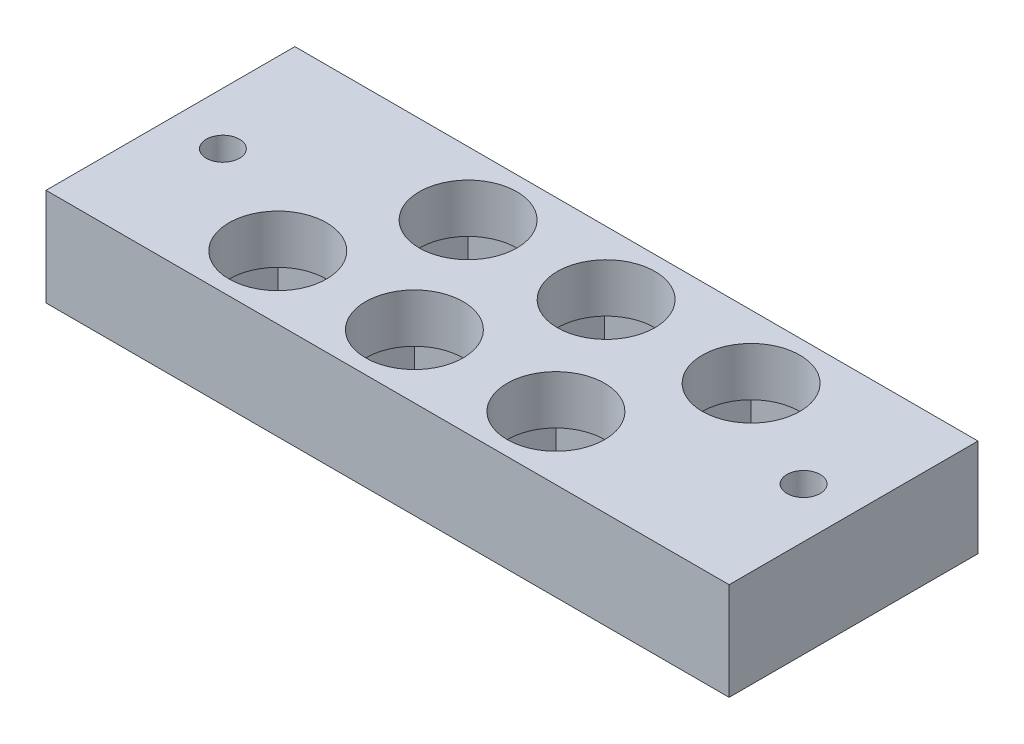
SolidWorks part; units mm, degrees
ref_plane "Front Plane" through (0, 0, 0) normal (0, 0, 1) x (1, 0, 0)
ref_plane "Top Plane" through (0, 0, 0) normal (0, 1, 0) x (1, 0, 0)
ref_plane "Right Plane" through (0, 0, 0) normal (1, 0, 0) x (0, 0, -1)
sketch "Sketch1" plane through (0, 0, 0) normal (0, 1, 0) x (1, 0, 0)
  line L0 (-35, 12.75) -> (-35, -12.75)
  line L1 (-35, -12.75) -> (35, -12.75)
  line L2 (35, -12.75) -> (35, 12.75)
  line L3 (35, 12.75) -> (-35, 12.75)
  line L4 (-23.75, -0.25) -> (-23.75, -12.25)
  line L5 (-23.75, -12.25) -> (-11.75, -12.25)
  line L6 (-11.75, -12.25) -> (-11.75, -0.25)
  line L7 (-11.75, -0.25) -> (-23.75, -0.25)
  line L8 (-9.75, -0.25) -> (-9.75, -12.25)
  line L9 (-9.75, -12.25) -> (2.25, -12.25)
  line L10 (2.25, -12.25) -> (2.25, -0.25)
  line L11 (2.25, -0.25) -> (-9.75, -0.25)
  line L12 (4.75, -0.25) -> (16.75, -0.25)
  line L13 (16.75, -0.25) -> (16.75, -12.25)
  line L14 (16.75, -12.25) -> (4.75, -12.25)
  line L15 (4.75, -12.25) -> (4.75, -0.25)
  line L16 (12.25, 12.25) -> (24.25, 12.25)
  line L17 (24.25, 12.25) -> (24.25, 0.25)
  line L18 (24.25, 0.25) -> (12.25, 0.25)
  line L19 (12.25, 0.25) -> (12.25, 12.25)
  line L20 (9.25, 12.25) -> (-2.75, 12.25)
  line L21 (-2.75, 12.25) -> (-2.75, 0.25)
  line L22 (-2.75, 0.25) -> (9.25, 0.25)
  line L23 (9.25, 0.25) -> (9.25, 12.25)
  line L24 (-16.75, 12.25) -> (-4.75, 12.25)
  line L25 (-4.75, 12.25) -> (-4.75, 0.25)
  line L26 (-4.75, 0.25) -> (-16.75, 0.25)
  line L27 (-16.75, 0.25) -> (-16.75, 12.25)
  circle A0 centre (-29.625, 0) radius 1.7
  circle A1 centre (29.875, 0) radius 1.7
  circle A2 centre (-17.75, -6.25) radius 5
  circle A3 centre (-3.75, -6.25) radius 5
  circle A4 centre (10.75, -6.25) radius 5
  circle A5 centre (-10.75, 6.25) radius 5
  circle A6 centre (3.3945, 6.25) radius 5
  circle A7 centre (18.25, 6.25) radius 5
  dimension "D1" = 10
  dimension "D3" = 5.875
  dimension "D2" = 5.625
extrude "Boss-Extrude1" add sketch "Sketch1" against normal blind 10 contours L2 L3 L0 L1 A1 A0 L23 L22 L21 L20 L11 L10 L9 L8 L7 L6 L5 L4 L14 L15 L12 L13 L18 L19 L16 L17 L26 L27 L24 L25 region at (-0.0025, 0, 0)
extrude "Boss-Extrude2" add sketch "Sketch1<3>" against normal blind 5 contours L27 L26 L25 L24 A5 | L22 L23 L20 L21 A6 | L19 L18 L17 L16 A7 | L15 L14 L13 L12 A4 | L10 L11 L8 L9 A3 | L6 L7 L4 L5 A2 region at (-17.75, 0, 0.4197) region at (-3.75, 0, 0.4197) region at (10.75, 0, 0.4197) region at (18.25, 0, -12.0803) region at (9.0803, 0, -6.25) region at (-10.75, 0, -12.0803)
sketch "Sketch1<3>" plane through (0, 0, 0) normal (0, 1, 0) x (1, 0, 0) same geometry as "Sketch1"
